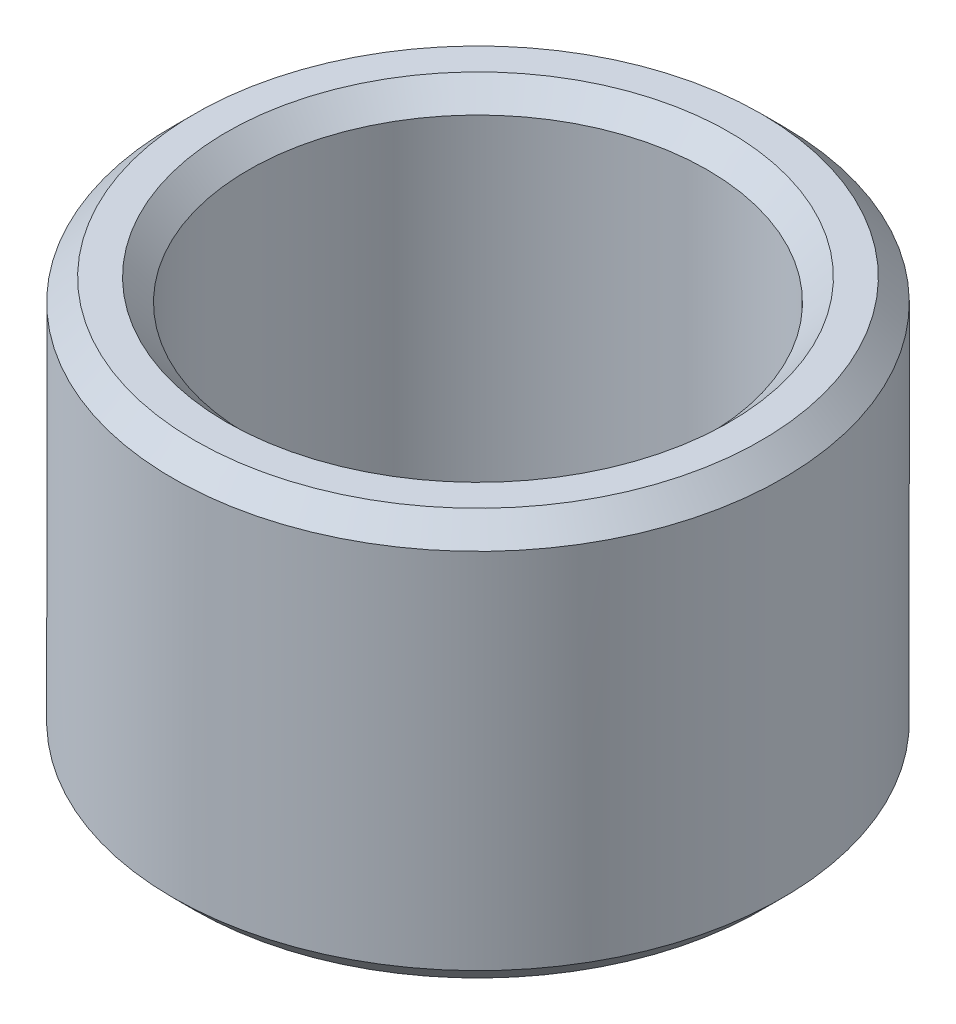
SolidWorks part; units mm, degrees
ref_plane "Front Plane" through (0, 0, 0) normal (0, 0, 1) x (1, 0, 0)
ref_plane "Top Plane" through (0, 0, 0) normal (0, 1, 0) x (1, 0, 0)
ref_plane "Right Plane" through (0, 0, 0) normal (1, 0, 0) x (0, 0, -1)
sketch "Sketch1" plane through (0, 0, 0) normal (0, 1, 0) x (1, 0, 0)
  circle A0 centre (0, 0) radius 10
  dimension "SLEEVE_OD" = 20
extrude "Boss-Extrude1" add sketch "Sketch1" along normal blind 13.3388
sketch "Sketch2" plane through (0, 0, 0) normal (0, 1, 0) x (1, 0, 0)
  circle A0 centre (0, 0) radius 7.5246
  dimension "BORE_D" = 15.0491
extrude "Cut-Extrude1" cut sketch "Sketch2" along normal through all
chamfer "Chamfer1" distance 0.717 angle 45 4 edges at (0, 13.3388, 7.5246) (0, 0, 7.5246) (0, 0, 10) (0, 13.3388, 10)
